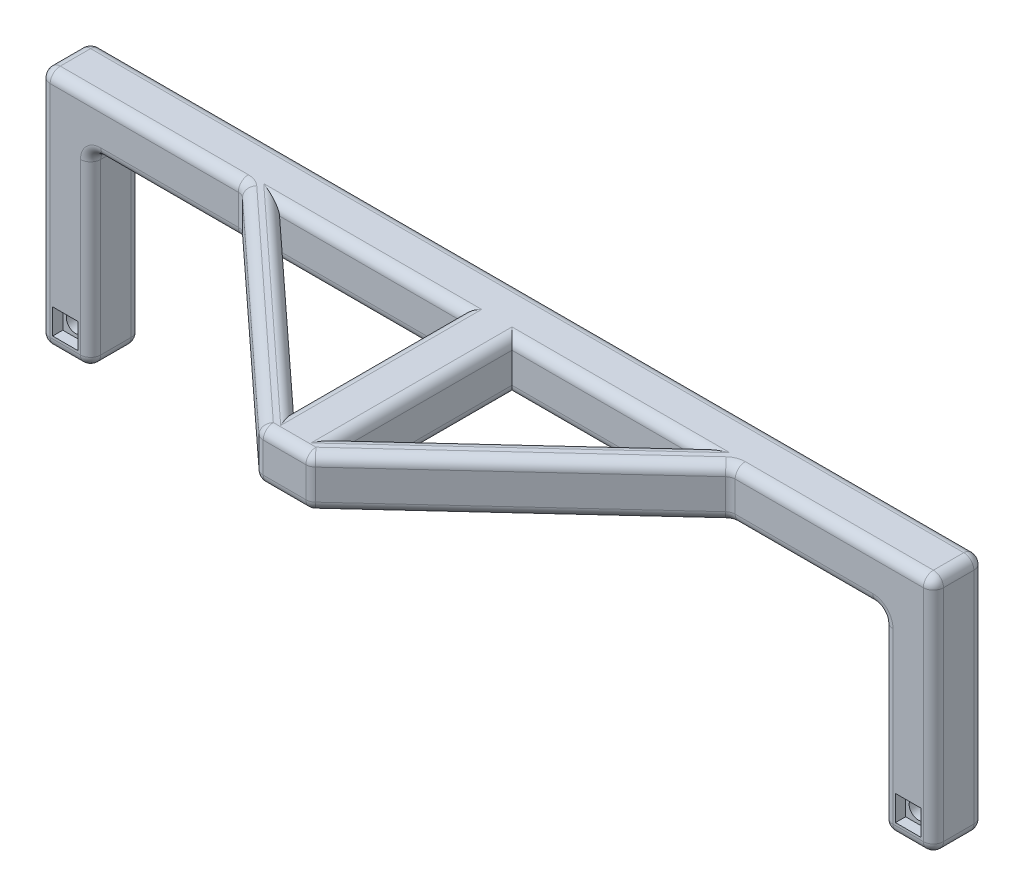
SolidWorks part; units mm, degrees
ref_plane "Front Plane" through (0, 0, 0) normal (0, 0, 1) x (1, 0, 0)
ref_plane "Top Plane" through (0, 0, 0) normal (0, 1, 0) x (1, 0, 0)
ref_plane "Right Plane" through (0, 0, 0) normal (1, 0, 0) x (0, 0, -1)
sketch "Sketch1" plane through (0, 0, 0) normal (0, 0, 1) x (1, 0, 0)
  line L1 (0, 0) -> (224.4725, 0)
  line L2 (0, 0) -> (0, 12.7)
  line L3 (0, 12.7) -> (224.4725, 12.7)
  line L4 (224.4725, 0) -> (224.4725, 12.7)
  dimension "D1" = 224.4725
  dimension "D2" = 12.7
extrude "Boss-Extrude1" add sketch "Sketch1" along normal blind 12.7
ref_plane "Plane1" through (112.2362, 0, 0) normal (-1, 0, 0) x (0, 0, 1)
sketch "Sketch2" plane through (0, 0, 0) normal (0, -1, 0) x (1, 0, 0)
  line L0 (0, 12.7) -> (224.4725, 12.7) construction
  line L1 (0, 0) -> (12.7, 0)
  line L2 (0, 0) -> (0, 12.7)
  line L3 (0, 12.7) -> (12.7, 12.7)
  line L4 (12.7, 0) -> (12.7, 12.7)
  dimension "D1" = 12.7
extrude "Boss-Extrude2" add sketch "Sketch2" along normal blind 47.625
sketch "Sketch3" plane through (0, 0, 12.7) normal (0, 0, 1) x (1, 0, 0)
  line L0 (12.7, -47.625) -> (0, -47.625) construction
  line L1 (0, 12.7) -> (0, -47.625) construction
  circle A0 centre (6.35, -41.275) radius 2.286
  dimension "D3" = 4.572
  dimension "D1" = 6.35
  dimension "D2" = 6.35
extrude "Cut-Extrude1" cut sketch "Sketch3" against normal through all
sketch "Sketch4" plane through (0, 0, 12.7) normal (0, 0, 1) x (1, 0, 0)
  line L1 (3.175, -38.1) -> (9.525, -38.1)
  line L2 (3.175, -38.1) -> (3.175, -44.45)
  line L3 (3.175, -44.45) -> (9.525, -44.45)
  line L4 (9.525, -38.1) -> (9.525, -44.45)
  line L5 (3.175, -38.1) -> (9.525, -44.45) construction
  line L6 (3.175, -44.45) -> (9.525, -38.1) construction
  point P0 (6.35, -41.275)
  dimension "D1" = 6.35
  dimension "D2" = 6.35
extrude "Cut-Extrude2" cut sketch "Sketch4" against normal blind 2.54
mirror "Mirror1" about plane through (112.2362, 0, 0) normal (-1, 0, 0) of "Cut-Extrude2", "Cut-Extrude1", "Boss-Extrude2"
sketch "Sketch5" plane through (0, 12.7, 0) normal (0, 1, 0) x (1, 0, 0)
  line L0 (50.8, -12.7) -> (105.8862, -63.5)
  line L2 (105.8862, -63.5) -> (118.5863, -63.5)
  line L3 (118.5863, -63.5) -> (173.6725, -12.7)
  line L11 (50.8, -12.7) -> (173.6725, -12.7)
  line L14 (224.4725, -12.7) -> (0, -12.7) construction
  dimension "D1" = 12.7
  dimension "D2" = 50.8
  dimension "D3" = 50.8
  dimension "D4" = 50.8
extrude "Boss-Extrude3" add sketch "Sketch5" against normal blind 12.7
sketch "Sketch7" plane through (0, 12.7, 0) normal (0, 1, 0) x (1, 0, 0)
  line L0 (60.1668, -12.7) -> (105.8863, -54.8621)
  line L1 (105.8863, -54.8621) -> (105.8863, -12.7)
  line L2 (105.8863, -12.7) -> (60.1668, -12.7)
  line L3 (118.5863, -54.8621) -> (118.5863, -12.7)
  line L4 (118.5863, -12.7) -> (164.3057, -12.7)
  line L5 (164.3057, -12.7) -> (118.5863, -54.8621)
  line L7 (50.8, -12.7) -> (105.8862, -63.5) construction
  line L8 (118.5863, -63.5) -> (173.6725, -12.7) construction
  line L9 (50.8, -12.7) -> (0, -12.7) construction
  line L10 (224.4725, -12.7) -> (173.6725, -12.7) construction
  dimension "D1" = 6.35
  dimension "D2" = 6.35
  dimension "D3" = 12.7
extrude "Cut-Extrude4" cut sketch "Sketch7" against normal blind 12.7
fillet "Fillet1" radius 2.54 48 edges at (12.7, -23.8125, 0) (12.7, -23.8125, 12.7) (211.7725, -23.8125, 12.7) (211.7725, -23.8125, 0) (0, -17.4625, 12.7) (0, -17.4625, 0) (224.4725, -17.4625, 12.7) (224.4725, -17.4625, 0) (218.1225, -47.625, 0) (211.7725, -47.625, 6.35) (218.1225, -47.625, 12.7) (224.4725, -47.625, 6.35) (6.35, -47.625, 12.7) (12.7, -47.625, 6.35) (6.35, -47.625, 0) (0, -47.625, 6.35) (12.7, 0, 6.35) (31.75, 0, 12.7) (192.7225, 0, 12.7) (211.7725, 0, 6.35) (112.2362, 0, 0) (141.446, 0, 12.7) (141.446, 0, 33.781) (118.5863, 0, 33.781) (83.0265, 0, 33.781) (83.0265, 0, 12.7) (105.8862, 0, 33.781) (78.3431, 0, 38.1) (50.8, 6.35, 12.7) (173.6725, 6.35, 12.7) (146.1294, 0, 38.1) (118.5863, 6.35, 63.5) (112.2362, 0, 63.5) (105.8862, 6.35, 63.5) (224.4725, 12.7, 6.35) (199.0725, 12.7, 12.7) (146.1294, 12.7, 38.1) (112.2362, 12.7, 63.5) (78.3431, 12.7, 38.1) (25.4, 12.7, 12.7) (0, 12.7, 6.35) (112.2362, 12.7, 0) (118.5863, 12.7, 33.781) (141.446, 12.7, 33.781) (141.446, 12.7, 12.7) (105.8863, 12.7, 33.781) (83.0265, 12.7, 12.7) (83.0265, 12.7, 33.781)
